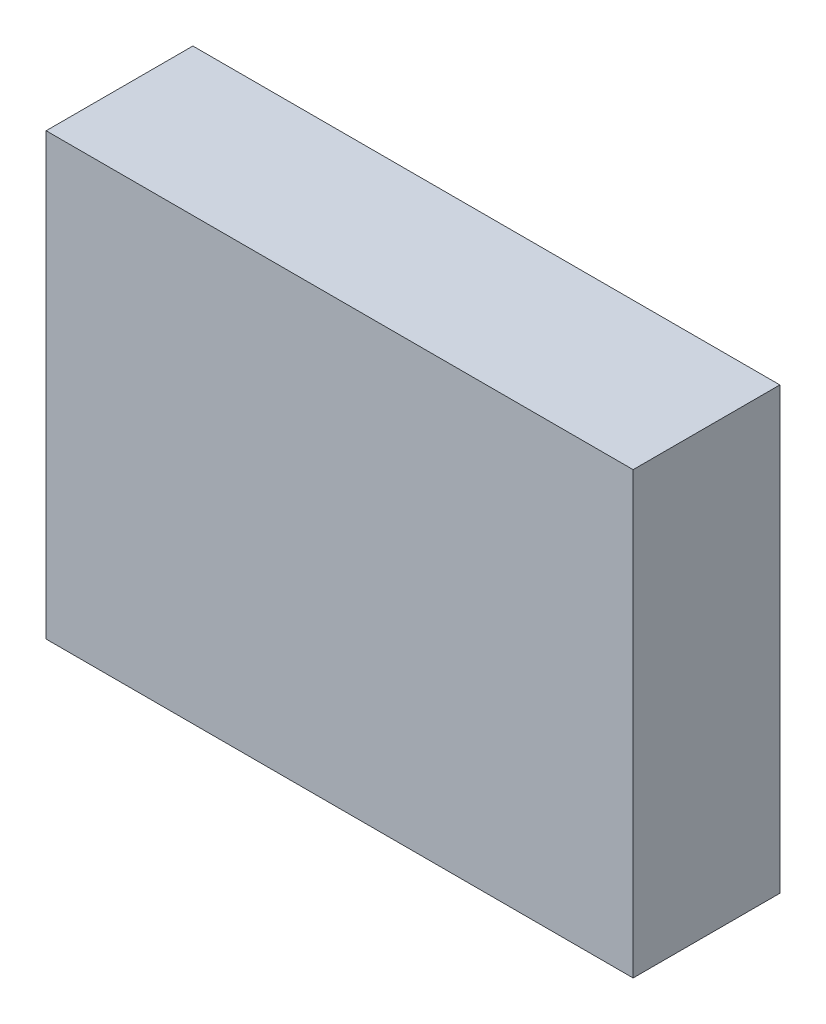
SolidWorks part; units mm, degrees
ref_plane "Front Plane" through (0, 0, 0) normal (0, 0, 1) x (1, 0, 0)
ref_plane "Top Plane" through (0, 0, 0) normal (0, 1, 0) x (1, 0, 0)
ref_plane "Right Plane" through (0, 0, 0) normal (1, 0, 0) x (0, 0, -1)
sketch "Sketch1" plane through (0, 0, 0) normal (0, 0, 1) x (1, 0, 0)
  line L1 (-50.8, -38.1) -> (50.8, -38.1)
  line L2 (-50.8, -38.1) -> (-50.8, 38.1)
  line L3 (-50.8, 38.1) -> (50.8, 38.1)
  line L4 (50.8, -38.1) -> (50.8, 38.1)
  line L5 (-50.8, -38.1) -> (50.8, 38.1) construction
  line L6 (-50.8, 38.1) -> (50.8, -38.1) construction
  point P0 (0, 0)
  dimension "D1" = 101.6
  dimension "D2" = 76.2
extrude "Boss-Extrude1" add sketch "Sketch1" along normal blind 25.4
sketch "Sketch2" plane through (0, 0, 0) normal (0, 0, -1) x (-1, 0, 0)
  line L1 (-45.72, 33.02) -> (45.72, 33.02)
  line L2 (-45.72, 33.02) -> (-45.72, -33.02)
  line L3 (-45.72, -33.02) -> (45.72, -33.02)
  line L4 (45.72, 33.02) -> (45.72, -33.02)
  line L5 (-45.72, 33.02) -> (45.72, -33.02) construction
  line L6 (-45.72, -33.02) -> (45.72, 33.02) construction
  circle A0 centre (45.72, -33.02) radius 2.794
  circle A1 centre (-45.72, -33.02) radius 2.794
  circle A2 centre (-45.72, 33.02) radius 2.794
  circle A3 centre (45.72, 33.02) radius 2.794
  point P0 (0, 0)
  dimension "D3" = 5.588
  dimension "D4" = 5.588
  dimension "D5" = 5.588
  dimension "D6" = 5.588
  dimension "D1" = 66.04
  dimension "D2" = 91.44
extrude "Cut-Extrude1" cut sketch "Sketch2" against normal blind 10.16 contours A0 | A3 | A2 | A1
shell "Shell1" thickness 2.54 removed face at (-48.514, 33.02, 0)
sketch "Sketch3" plane through (0, 0, 0) normal (0, 0, 1) x (1, 0, 0)
sketch_block_instance "Logo-1"
sketch_block "Logo"
